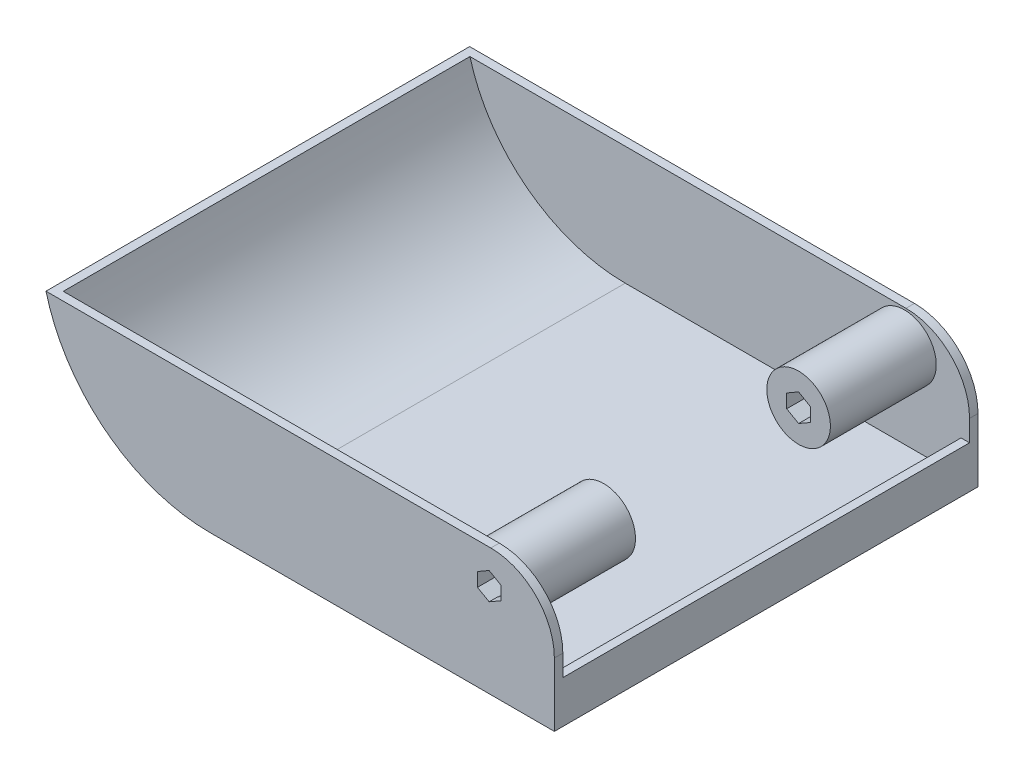
SolidWorks part; units mm, degrees
ref_plane "Front Plane" through (0, 0, 0) normal (0, 0, 1) x (1, 0, 0)
ref_plane "Top Plane" through (0, 0, 0) normal (0, 1, 0) x (1, 0, 0)
ref_plane "Right Plane" through (0, 0, 0) normal (1, 0, 0) x (0, 0, -1)
sketch "Sketch1" plane through (0, 0, 0) normal (0, 1, 0) x (1, 0, 0)
  line L1 (-76.2, -63.5) -> (76.2, -63.5)
  line L2 (-76.2, -63.5) -> (-76.2, 63.5)
  line L3 (-76.2, 63.5) -> (76.2, 63.5)
  line L4 (76.2, -63.5) -> (76.2, 63.5)
  dimension "D1" = 63.5
  dimension "D2" = 63.5
  dimension "D3" = 152.4
  dimension "D4" = 76.2
extrude "Boss-Extrude1" add sketch "Sketch1" along normal blind 38.1
fillet "Fillet1" radius 50.8 1 edges at (-76.2, 0, 0)
shell "Shell1" thickness 2.54 removed face at (0, 38.1, 0)
sketch "Sketch2" plane through (0, 38.1, 0) normal (0, 1, 0) x (1, 0, 0)
  line L0 (73.66, 60.96) -> (-27.0131, 60.96) construction
  line L1 (72.4364, 60.96) -> (84.0499, 60.96)
  line L2 (72.4364, 60.96) -> (72.4364, -60.96)
  line L3 (72.4364, -60.96) -> (84.0499, -60.96)
  line L4 (84.0499, 60.96) -> (84.0499, -60.96)
  line L5 (-27.0131, -60.96) -> (73.66, -60.96) construction
  dimension "D1" = 0
sketch "Sketch3" plane through (0, 0, -60.96) normal (0, 0, 1) x (1, 0, 0)
  line L0 (73.66, 2.54) -> (-27.0131, 2.54) construction
  line L4 (56.5722, 32.0461) -> (53.0162, 29.9931)
  line L5 (53.0162, 29.9931) -> (53.0162, 25.8869)
  line L6 (53.0162, 25.8869) -> (56.5722, 23.8339)
  line L7 (56.5722, 23.8339) -> (60.1282, 25.8869)
  line L8 (60.1282, 25.8869) -> (60.1282, 29.9931)
  line L9 (60.1282, 29.9931) -> (56.5722, 32.0461)
  circle A1 centre (56.5722, 27.94) radius 3.556 construction
  dimension "D3" = 7.112
  dimension "D1" = 25.4
extrude "Cut-Extrude2" cut sketch "Sketch3" against normal through all both and the other way through all
sketch "Sketch4" plane through (0, 0, -60.96) normal (0, 0, 1) x (1, 0, 0)
  line L0 (73.66, 2.54) -> (-27.0131, 2.54) construction
  line L2 (56.7069, 32.0461) -> (53.1509, 29.9931)
  line L3 (53.1509, 29.9931) -> (53.1509, 25.8869)
  line L4 (53.1509, 25.8869) -> (56.7069, 23.8339)
  line L5 (56.7069, 23.8339) -> (60.2629, 25.8869)
  line L6 (60.2629, 25.8869) -> (60.2629, 29.9931)
  line L7 (60.2629, 29.9931) -> (56.7069, 32.0461)
  circle A0 centre (56.7069, 27.94) radius 9.525
  circle A1 centre (56.7069, 27.94) radius 3.556 construction
  dimension "D2" = 19.05
  dimension "D3" = 7.112
  dimension "D1" = 25.4
extrude "Boss-Extrude2" add sketch "Sketch4" along normal blind 124.46
extrude "Cut-Extrude3" cut sketch "Sketch2" against normal blind 25.4
sketch "Sketch5" plane through (0, 2.54, 0) normal (0, 1, 0) x (1, 0, 0)
  line L0 (-27.0131, -60.96) -> (73.66, -60.96) construction
  line L1 (39.391, -29.21) -> (68.4728, -29.21)
  line L2 (39.391, -29.21) -> (39.391, 29.21)
  line L3 (39.391, 29.21) -> (68.4728, 29.21)
  line L4 (68.4728, -29.21) -> (68.4728, 29.21)
  line L5 (73.66, 60.96) -> (-27.0131, 60.96) construction
  dimension "D1" = 31.75
  dimension "D2" = 31.75
extrude "Cut-Extrude4" cut sketch "Sketch5" along normal blind 50.8 contours L2 L3 L4 L1
fillet "Fillet3" radius 19.05 2 edges at (76.2, 38.1, -62.23) (76.2, 38.1, 62.23)
